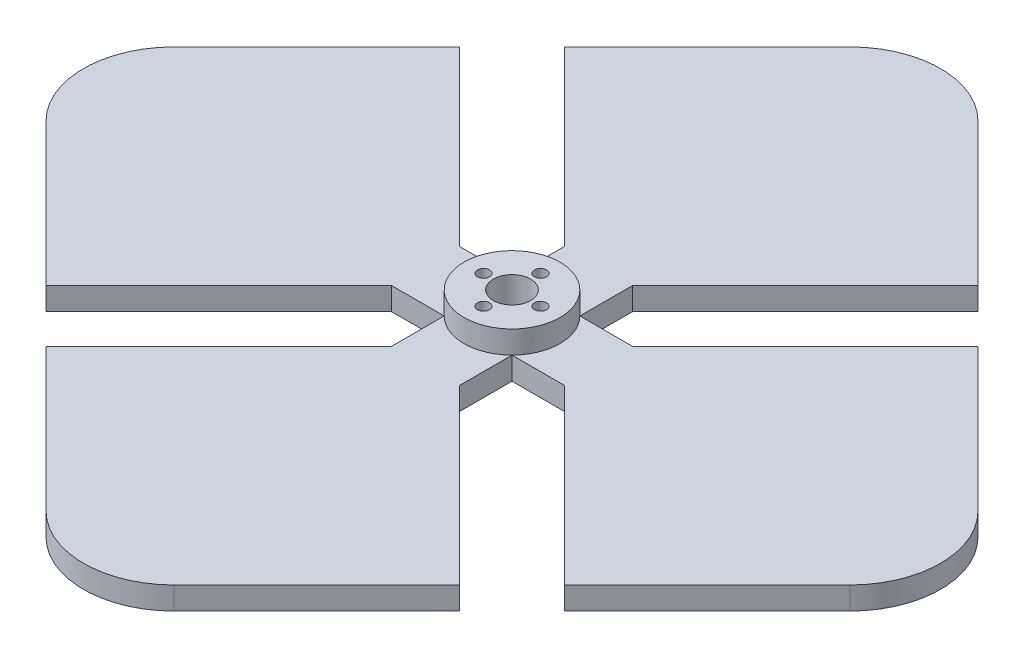
SolidWorks part; units mm, degrees
ref_plane "Front Plane" through (0, 0, 0) normal (0, 0, 1) x (1, 0, 0)
ref_plane "Top Plane" through (0, 0, 0) normal (0, 1, 0) x (1, 0, 0)
ref_plane "Right Plane" through (0, 0, 0) normal (1, 0, 0) x (0, 0, -1)
sketch "Sketch4" plane through (0, 0, 0) normal (0, 1, 0) x (1, 0, 0)
  line L8 (14.7955, 0) -> (72.808, -58.0125)
  line L9 (14.7955, 0) -> (72.808, 58.0125)
  line L10 (72.808, -58.0125) -> (130.8204, 0)
  line L11 (72.808, 58.0125) -> (130.8204, 0)
  line L13 (0, 9.525) -> (24.3205, 9.525)
  line L14 (0, 9.525) -> (0, -9.525)
  line L15 (0, -9.525) -> (24.3205, -9.525)
  line L16 (24.3205, 9.525) -> (24.3205, -9.525)
  dimension "D1" = 82.042
  dimension "D2" = 14.7955
  dimension "D3" = 19.05
extrude "Boss-Extrude5" add sketch "Sketch4" along normal blind 6.35 contours L9 L16 L8 L10 L11 | L16 L9 L8 | L14 L15 L8 L9 L13 region at (21.1455, 0, 0) region at (9.9723, 0, 0) region at (73.5138, 0, 0)
sketch "Sketch6" plane through (0, 0, 0) normal (0, 0, 1) x (1, 0, 0)
  line L0 (0, 0) -> (0, 27.64) construction
fillet "Fillet1" radius 25.4 1 edges at (130.8204, 3.175, 0)
pattern_circular "CirPattern7" count 4 over 360 about axis through (0, 0, 0) along (0, 1, 0) of "Boss-Extrude5", "Fillet1"
sketch "Sketch13" plane through (0, 6.35, 0) normal (0, 1, 0) x (1, 0, 0)
  circle A0 centre (0, 0) radius 13.4704
extrude "Boss-Extrude8" add sketch "Sketch13" along normal blind 6.35
sketch "Sketch1" plane through (0, 0, 0) normal (0, 1, 0) x (1, 0, 0)
  circle A0 centre (0, 0) radius 2.6905 construction
  circle A1 centre (0, 0) radius 5.227
  circle A2 centre (8, 0) radius 1.6865
  circle A6 centre (0, -8) radius 1.6865
  circle A7 centre (-8, 0) radius 1.6865
  circle A8 centre (0, 8) radius 1.6865
  point P15 (0, 0)
  dimension "D1" = 10.454
  dimension "D3" = 3.373
  dimension "D2" = 8
extrude "Cut-Extrude1" cut sketch "Sketch1" along normal through all
equation "\"tightTol\"= 0.005in"
equation "\"normTol\"= 0.01in"
equation "\"looseTol\"= 0.02in"
equation "\"D1@Sketch1\"=\"normTol\"+10.2mm"
equation "\"D2@Sketch1\"=8mm"
equation "\"D1@Sketch4\"=3.25-\"looseTol\""
equation "\"D2@Sketch4\"=9/16+\"looseTol\""
equation "\"D3@Sketch1\"=3.5mm-\"tightTol\""
